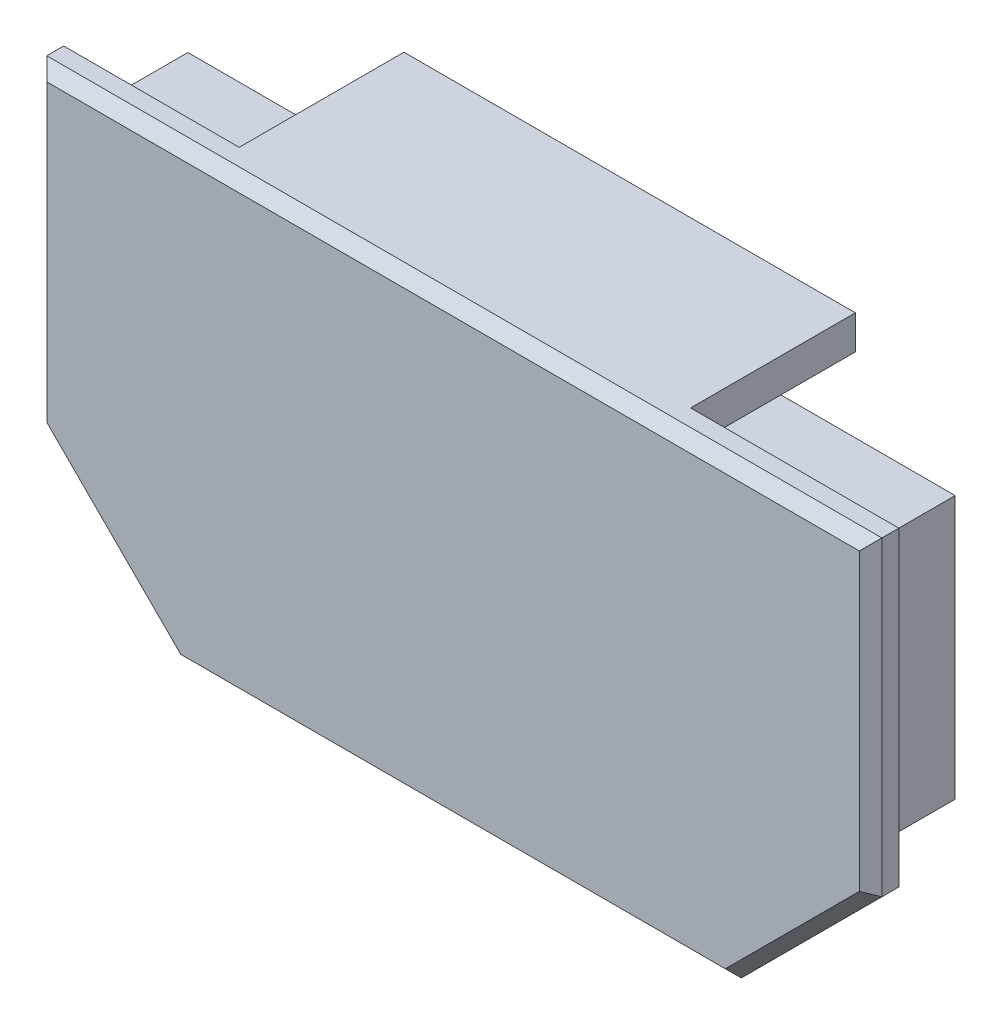
SolidWorks part; units mm, degrees
material "ABS"
ref_plane "Front Plane" through (0, 0, 0) normal (0, 0, 1) x (1, 0, 0)
ref_plane "Top Plane" through (0, 0, 0) normal (0, 1, 0) x (1, 0, 0)
ref_plane "Right Plane" through (0, 0, 0) normal (1, 0, 0) x (0, 0, -1)
sketch "Servo Bracket Reference" plane through (0, 0, 0) normal (0, 0, 1) x (1, 0, 0)
  line L0 (-37, 20) -> (37, 20) construction
  line L1 (-37, -3.3) -> (-20.3, -20) construction
  line L34 (-37, 20) -> (-37, -7.5426) construction
  line L35 (-37, -7.5426) -> (-24.5426, -20) construction
  line L36 (-24.5426, -20) -> (24.5426, -20) construction
  line L37 (24.5426, -20) -> (37, -7.5426) construction
  line L38 (37, -7.5426) -> (37, 20) construction
  point P0 (0, 20)
  point P4 (0, 0)
  dimension "D3" = 74
  dimension "D1" = 40
  dimension "D5" = 20
  dimension "D2" = 3
  dimension "D4" = 16.7
sketch "Sketch2" plane through (0, 0, 0) normal (0, 0, 1) x (1, 0, 0)
  line L18 (37, -7.5426) -> (37, 20) construction
  line L19 (24.5426, -20) -> (37, -7.5426) construction
  line L20 (-24.5426, -20) -> (24.5426, -20) construction
  line L21 (-37, 20) -> (-37, -7.5426) construction
  line L22 (-37, -7.5426) -> (-24.5426, -20) construction
  line L23 (-37, 20) -> (37, 20) construction
  line L24 (37, -7.5426) -> (37, 20) construction
  line L25 (24.5426, -20) -> (37, -7.5426) construction
  line L26 (-24.5426, -20) -> (24.5426, -20) construction
  line L27 (-37, 20) -> (-37, -7.5426) construction
  line L28 (-37, -7.5426) -> (-24.5426, -20) construction
  line L29 (-37, 20) -> (37, 20) construction
  line L36 (34, -6.3) -> (34, 17)
  line L37 (-34, 17) -> (34, 17)
  line L38 (-34, 17) -> (-34, -6.3)
  line L39 (-34, -6.3) -> (-23.3, -17)
  line L40 (-23.3, -17) -> (23.3, -17)
  line L41 (23.3, -17) -> (34, -6.3)
  line L42 (32, -5.4716) -> (32, 15)
  line L43 (-32, 15) -> (32, 15)
  line L44 (-32, 15) -> (-32, -5.4716)
  line L45 (-32, -5.4716) -> (-22.4716, -15)
  line L46 (-22.4716, -15) -> (22.4716, -15)
  line L47 (22.4716, -15) -> (32, -5.4716)
  dimension "D1" = 3
  dimension "D2" = 2
extrude "Press Fit Wall Extrude" add sketch "Sketch2" against normal blind 8
sketch "Sketch3" plane through (0, 0, 0) normal (0, 0, 1) x (1, 0, 0)
  line L6 (24.5426, -20) -> (37, -7.5426) construction
  line L7 (37, -7.5426) -> (37, 20) construction
  line L8 (-37, 20) -> (37, 20) construction
  line L9 (-37, 20) -> (-37, -7.5426) construction
  line L10 (-37, -7.5426) -> (-24.5426, -20) construction
  line L11 (-24.5426, -20) -> (24.5426, -20) construction
  line L24 (24.5426, -20) -> (37, -7.5426)
  line L25 (37, -7.5426) -> (37, 20)
  line L26 (-37, 20) -> (37, 20)
  line L27 (-37, 20) -> (-37, -7.5426)
  line L28 (-37, -7.5426) -> (-24.5426, -20)
  line L29 (-24.5426, -20) -> (24.5426, -20)
extrude "Main Lid Extrude" add sketch "Sketch3" along normal blind 2.5
chamfer "Main Lid Chamfer" distance 1 angle 45 6 edges at (37, 6.2287, 2.5) (30.7713, -13.7713, 2.5) (-30.7713, -13.7713, 2.5) (-37, 6.2287, 2.5) (0, 20, 2.5) (0, -20, 2.5)
sketch "Sketch4" plane through (0, -20, 0) normal (0, -1, 0) x (1, 0, 0)
  line L0 (-4, 0) -> (4, 0)
  line L5 (-37, 0) -> (37, 0) construction
  line L6 (4, 0) -> (2.2679, 1)
  line L7 (2.2679, 1) -> (-2.2679, 1)
  line L8 (-2.2679, 1) -> (-4, 0)
  point P4 (0, 0)
  point P8 (1.8704, 0.8792)
  dimension "D1" = 8
  dimension "D2" = 30
  dimension "D3" = 1
extrude "Main Lid Tab Cut" cut sketch "Sketch4" against normal up to surface (3 mm away) up to face at (0, -17, -4)
sketch "Sketch5" plane through (0, 0, 0) normal (0, 0, -1) x (-1, 0, 0)
  line L0 (-37, 20) -> (37, 20) construction
  line L1 (-18.55, 20) -> (21.45, 20)
  line L2 (-18.55, 20) -> (-18.55, 17)
  line L3 (-18.55, 17) -> (21.45, 17)
  line L4 (21.45, 20) -> (21.45, 17)
  line L5 (-34, 17) -> (34, 17) construction
  line L7 (-37, -7.5426) -> (-37, 20) construction
  dimension "D1" = 40
  dimension "D2" = 18.45
extrude "Servo Wall Extrude" add sketch "Sketch5" along normal blind 14.6
equation "\"D5@Servo Bracket Reference\"=\"D1@Servo Bracket Reference\"/2"
